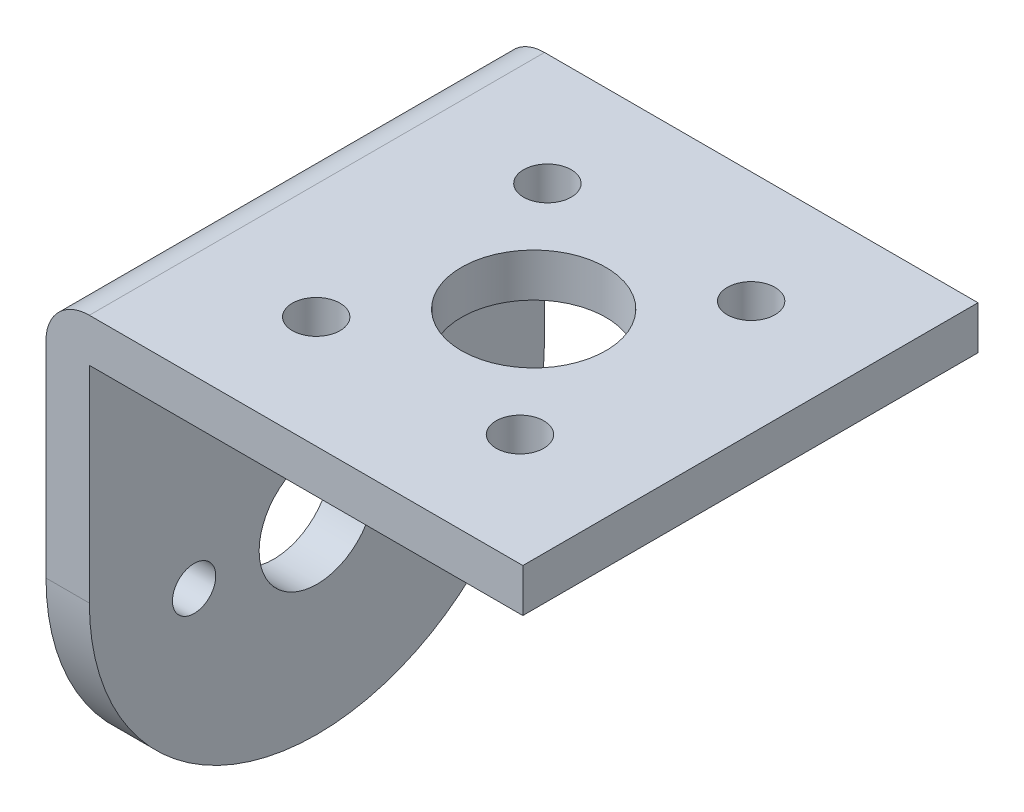
SolidWorks part; units mm, degrees
ref_plane "Alzado" through (0, 0, 0) normal (0, 0, 1) x (1, 0, 0)
ref_plane "Planta" through (0, 0, 0) normal (0, 1, 0) x (1, 0, 0)
ref_plane "Vista lateral" through (0, 0, 0) normal (1, 0, 0) x (0, 0, -1)
sketch "Sketch1" plane through (0, 0, 0) normal (0, 1, 0) x (1, 0, 0)
  line L0 (23, 31.5) -> (23, 0) construction
  line L1 (0, 0) -> (33, 0)
  line L2 (0, 0) -> (0, 31.5)
  line L3 (0, 31.5) -> (33, 31.5)
  line L4 (33, 0) -> (33, 31.5)
  line L5 (26.7, 31.5) -> (26.7, 0) construction
  line L6 (12.6, 31.5) -> (12.6, 23.75) construction
  line L7 (23.4, 31.5) -> (23.4, 23.75) construction
  line L8 (23.4, 25.4) -> (26.7, 25.4) construction
  line L9 (0, 15.75) -> (33, 15.75) construction
  line L10 (10.95, 7.75) -> (25.05, 7.75) construction
  line L11 (25.05, 22.1) -> (33, 22.1) construction
  line L12 (25.05, 9.4) -> (33, 9.4) construction
  circle A0 centre (18, 15.75) radius 5
  circle A1 centre (25.05, 23.75) radius 1.65
  circle A2 centre (10.95, 23.75) radius 1.65
  circle A5 centre (25.05, 7.75) radius 1.65
  circle A6 centre (10.95, 7.75) radius 1.65
  point P8 (33, 15.75)
  point P28 (18, 7.75)
  dimension "D3" = 10
  dimension "D5" = 3.3
  dimension "D6" = 10.8
  dimension "D7" = 12.7
  dimension "D1" = 33
  dimension "D2" = 31.5
  dimension "D4" = 10
extrude "Boss-Extrude1" add sketch "Sketch1" along normal blind 3
sketch "Sketch2" plane through (0, 0, 0) normal (0, -1, 0) x (1, 0, 0)
  line L0 (33, -31.5) -> (0, -31.5) construction
  line L1 (0, 0) -> (3, 0)
  line L2 (0, 0) -> (0, -31.5)
  line L3 (0, -31.5) -> (3, -31.5)
  line L4 (3, 0) -> (3, -31.5)
  dimension "D1" = 3
extrude "Boss-Extrude2" add sketch "Sketch2" along normal blind 30
sketch "Sketch3" plane through (0, 0, 0) normal (-1, 0, 0) x (0, 0, 1)
  line L0 (-31.5, 3) -> (0, 3) construction
  line L1 (-24.25, -17) -> (-15.75, -17) construction
  line L2 (-15.75, -17) -> (-7.25, -17) construction
  line L3 (-31.5, -21) -> (0, -21) construction
  line L4 (-31.5, 3) -> (-31.5, -30) construction
  line L5 (0, 3) -> (0, -30) construction
  line L6 (0, -30) -> (-31.5, -30) construction
  line L7 (-8.75, 3) -> (-8.75, -30) construction
  line L8 (-11.75, 3) -> (-11.75, -30) construction
  circle A0 centre (-24.25, -17) radius 1.5
  circle A1 centre (-7.25, -17) radius 1.5
  circle A2 centre (-15.75, -17) radius 4
  point P10 (-15.75, 3)
  point P21 (-15.75, -30)
  dimension "D1" = 3
  dimension "D2" = 8
  dimension "D4" = 3
  dimension "D3" = 9
extrude "Cut-Extrude1" cut sketch "Sketch3" against normal blind 30
fillet "Fillet3" radius 15.75 2 edges at (1.5, -30, 0) (1.5, -30, -31.5)
fillet "Fillet4" radius 3 1 edges at (0, 3, -15.75)
